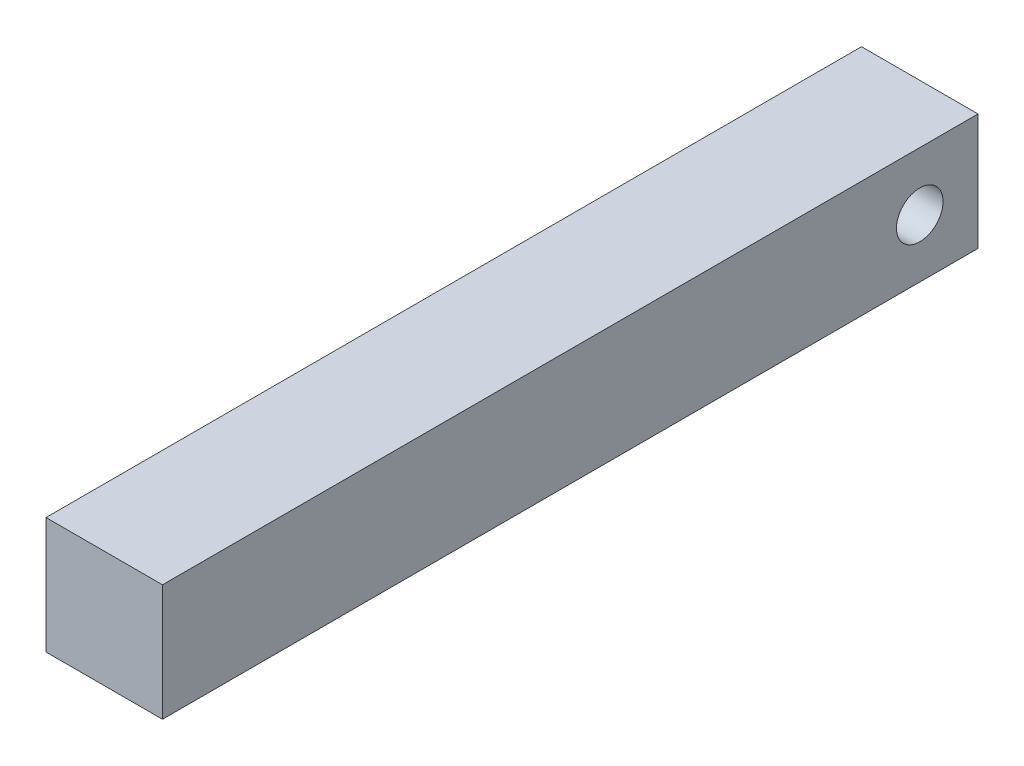
SolidWorks part; units mm, degrees
ref_plane "Front Plane" through (0, 0, 0) normal (0, 0, 1) x (1, 0, 0)
ref_plane "Top Plane" through (0, 0, 0) normal (0, 1, 0) x (1, 0, 0)
ref_plane "Right Plane" through (0, 0, 0) normal (1, 0, 0) x (0, 0, -1)
sketch "Sketch1" plane through (0, 0, 0) normal (0, 1, 0) x (1, 0, 0)
  line L1 (-2.5, 17.5) -> (2.5, 17.5)
  line L2 (-2.5, 17.5) -> (-2.5, -17.5)
  line L3 (-2.5, -17.5) -> (2.5, -17.5)
  line L4 (2.5, 17.5) -> (2.5, -17.5)
  line L5 (-2.5, 17.5) -> (2.5, -17.5) construction
  line L6 (-2.5, -17.5) -> (2.5, 17.5) construction
  point P0 (0, 0)
  dimension "D1" = 35
  dimension "D2" = 5
extrude "Boss-Extrude1" add sketch "Sketch1" along normal blind 5
sketch "Sketch2" plane through (2.5, 0, 0) normal (1, 0, 0) x (0, 0, -1)
  line L0 (17.5, 2.5) -> (0, 2.5) construction
  line L1 (17.5, 5) -> (17.5, 0) construction
  line L2 (15, 5) -> (15, 0) construction
  line L3 (-17.5, 5) -> (17.5, 5) construction
  line L4 (-17.5, 0) -> (17.5, 0) construction
  circle A0 centre (15, 2.5) radius 1
  dimension "D2" = 2
  dimension "D1" = 2.5
extrude "Cut-Extrude1" cut sketch "Sketch2" against normal through all
